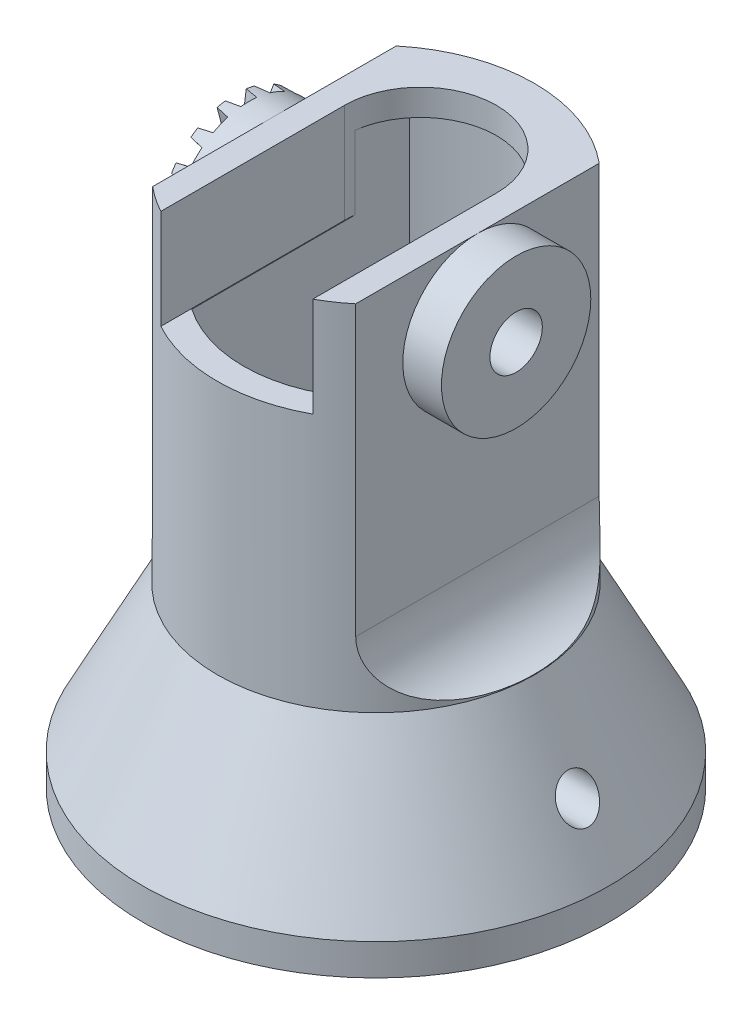
SolidWorks part; units mm, degrees
ref_plane "정면" through (0, 0, 0) normal (0, 0, 1) x (1, 0, 0)
ref_plane "윗면" through (0, 0, 0) normal (0, 1, 0) x (1, 0, 0)
ref_plane "우측면" through (0, 0, 0) normal (1, 0, 0) x (0, 0, -1)
sketch "스케치1" plane through (0, 0, 0) normal (0, 0, 1) x (1, 0, 0)
  line L0 (0, 0) -> (17.8, 0)
  line L1 (17.8, 0) -> (17.8, 2.4)
  line L2 (17.8, 2.4) -> (12.1, 13.5)
  line L3 (12.1, 13.5) -> (12.1, 40.5)
  line L4 (12.1, 40.5) -> (0, 40.5)
  line L5 (0, 40.5) -> (0, 0)
  dimension "D1" = 17.8
  dimension "D2" = 12.1
  dimension "D3" = 40.5
  dimension "D4" = 13.5
  dimension "D5" = 2.4
revolve "회전1" add sketch "스케치1" angle 360 about L5
sketch "스케치2" plane through (0, 0, 0) normal (0, 0, 1) x (1, 0, 0)
  line L0 (0, 0) -> (0, 41.8881) construction
  line L1 (-7.75, 41.8881) -> (-7.75, 18.5)
  line L2 (-12.75, 13.5) -> (-16.8515, 13.5)
  line L3 (-16.8515, 13.5) -> (-16.8515, 41.8881)
  line L4 (-16.8515, 41.8881) -> (-7.75, 41.8881)
  line L5 (7.75, 41.4037) -> (7.75, 18.5)
  line L6 (12.75, 13.5) -> (17.2189, 13.5)
  line L7 (17.2189, 13.5) -> (17.2189, 41.4037)
  line L8 (17.2189, 41.4037) -> (7.75, 41.4037)
  line L9 (-17.8, 0) -> (17.8, 0) construction
  arc A0 (12.75, 13.5) -> (7.75, 18.5) centre (12.75, 18.5) cw
  arc A1 (-7.75, 18.5) -> (-12.75, 13.5) centre (-12.75, 18.5) cw
  point P7 (-7.75, 41.8881)
  point P14 (-16.8515, 41.8881)
  dimension "D3" = 5
  dimension "D4" = 5
  dimension "D1" = 15.5
  dimension "D2" = 13.5
extrude "컷-돌출1" cut sketch "스케치2" against normal through all both and the other way through all
shell "쉘1" thickness 2 removed face at (-17.8, 0, 0)
sketch "스케치4" plane through (0, 0, 0) normal (1, 0, 0) x (0, 0, -1)
  circle A0 centre (0, 34.8) radius 5.7
  circle A1 centre (0, 34.8) radius 2
  point P3 (0, 0)
  dimension "D1" = 11.4
  dimension "D2" = 4
  dimension "D3" = 34.8
extrude "보스-돌출1" add sketch "스케치4" along normal blind 10.7 and the other way blind 10.7
sketch "스케치3" plane through (0, 40.5, 0) normal (0, 1, 0) x (1, 0, 0)
  line L0 (0, 3.4) -> (0, -21.0972) construction
  line L1 (5.8, 3.4) -> (5.8, -21.0972)
  line L2 (-5.8, 3.4) -> (-5.8, -21.0972)
  arc A0 (5.8, 3.4) -> (-5.8, 3.4) centre (0, 3.4) ccw
  arc A1 (-5.8, -21.0972) -> (5.8, -21.0972) centre (0, -21.0972) ccw
  arc A2 (7.75, 9.2923) -> (-7.75, 9.2923) centre (0, 0) ccw construction
  point P3 (0, -8.8486)
  point P8 (0, 3.3182)
  point P12 (0, -21.0972)
  dimension "D2" = 3.4
  dimension "D1" = 11.6
extrude "컷-돌출2" cut sketch "스케치3" against normal blind 7.6
sketch "스케치6" plane through (0, 0, 0) normal (0, 1, 0) x (1, 0, 0)
  line L0 (-5.75, -8.3035) -> (-5.75, 8.3035)
  line L1 (-5.75, 8.3035) -> (5.75, 8.3035)
  line L2 (5.75, 8.3035) -> (5.75, -8.3035)
  line L3 (5.75, -8.3035) -> (-5.75, -8.3035)
extrude "컷-돌출3" cut sketch "스케치6" along normal up to surface (38.5 mm away) up to face at (0, 38.5, -6.7685)
ref_plane "평면1" through (0, 2, 0) normal (0, -1, 0) x (-1, 0, 0)
sketch "스케치7" plane through (0, 2, 0) normal (0, -1, 0) x (-1, 0, 0)
  arc A0 (13, 0) -> (-13, 0) centre (0, 0) ccw
  circle A1 centre (0, 0) radius 11
  arc A5 (-13, 0) -> (13, 0) centre (0, 0) ccw
  point P1 (-12.52, -3.1811)
  point P4 (13, 0)
  point P5 (13, -0.3111)
  point P6 (-13, 0)
  point P10 (-17.5554, -4.0593)
  dimension "D1" = 22
  dimension "D2" = 26
extrude "보스-돌출4" add sketch "스케치7" against normal up to surface (9.2639 mm away) up to face at (0, 16.879, -0.2104)
sketch "스케치9" plane through (0, 2, 0) normal (0, -1, 0) x (-1, 0, 0)
  line L0 (-25.1686, 0) -> (25.3117, 0) construction
  line L1 (-15.3607, 3.7) -> (-12.4623, 3.7)
  line L3 (15.3607, -3.7) -> (12.4623, -3.7)
  line L4 (-12.4623, -3.7) -> (-15.3607, -3.7)
  line L5 (12.4623, 3.7) -> (15.3607, 3.7)
  arc A0 (-12.4623, 3.7) -> (-12.4623, -3.7) centre (0, 0) ccw
  arc A1 (-15.3607, 3.7) -> (-15.3607, -3.7) centre (0, 0) ccw
  arc A2 (15.3607, -3.7) -> (15.3607, 3.7) centre (0, 0) ccw
  arc A3 (12.4623, -3.7) -> (12.4623, 3.7) centre (0, 0) ccw
  circle A4 centre (0, 0) radius 13 construction
  circle A5 centre (0, 0) radius 15.8 construction
  dimension "D1" = 7.4
extrude "보스-돌출5" add sketch "스케치9" against normal up to surface (5.3691 mm away) up to face at (13, 7.3691, 0)
sketch "스케치10" plane through (0, 0, 0) normal (1, 0, 0) x (0, 0, -1)
  circle A0 centre (0, 7) radius 1.5
  point P2 (0, 0)
  dimension "D1" = 3
  dimension "D2" = 7
extrude "컷-돌출4" cut sketch "스케치10" against normal through all both and the other way through all
sketch "스케치11" plane through (-10.7, 0, 0) normal (-1, 0, 0) x (0, 0, 1)
  line L0 (0, 34.8) -> (0, 43.1582) construction
  line L1 (-0.9106, 41.2239) -> (-0.1891, 36.1343)
  line L2 (-0.1891, 36.1343) -> (0.1891, 36.1343)
  line L3 (0.1891, 36.1343) -> (0.9106, 41.2239)
  line L4 (0.9106, 41.2239) -> (-0.9106, 41.2239)
  circle A0 centre (0, 34.8) radius 5.7 construction
  circle A1 centre (0, 34.8) radius 5.7 construction
  point P8 (0.8, 40.4436)
  point P9 (-0.8, 40.4436)
  point P10 (0, 0)
  point P15 (0, 0)
  dimension "D1" = 1.6
extrude "컷-돌출5" cut sketch "스케치11" against normal blind 1 draft 11
pattern_circular "원형 패턴1" count 16 over 360 about axis through (-10.7, 34.8, 0) along (1, 0, 0) of "컷-돌출5"
